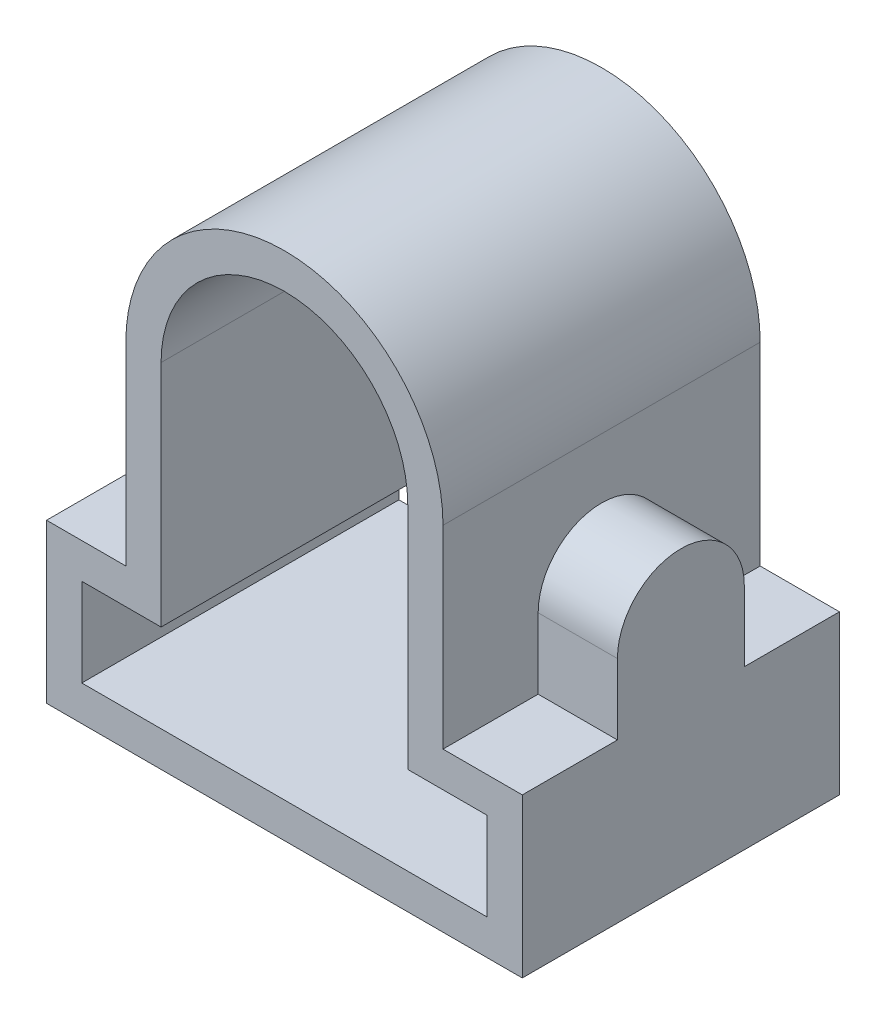
SolidWorks part; units mm, degrees
ref_plane "Front Plane" through (0, 0, 0) normal (0, 0, 1) x (1, 0, 0)
ref_plane "Top Plane" through (0, 0, 0) normal (0, 1, 0) x (1, 0, 0)
ref_plane "Right Plane" through (0, 0, 0) normal (1, 0, 0) x (0, 0, -1)
sketch "Sketch1" plane through (0, 0, 0) normal (0, 0, 1) x (1, 0, 0)
  line L0 (-67.5, 0) -> (67.5, 0)
  line L1 (67.5, 0) -> (67.5, 45)
  line L2 (67.5, 45) -> (45, 45)
  line L3 (45, 45) -> (45, 100)
  line L4 (0, 175.3726) -> (0, 0) construction
  line L5 (-67.5, 0) -> (-67.5, 45)
  line L6 (-67.5, 45) -> (-45, 45)
  line L7 (-45, 45) -> (-45, 100)
  line L8 (35, 35) -> (35, 100)
  line L9 (-35, 35) -> (-35, 100)
  line L10 (-57.5, 35) -> (-35, 35)
  line L11 (-57.5, 10) -> (-57.5, 35)
  line L12 (-57.5, 10) -> (57.5, 10)
  line L13 (57.5, 10) -> (57.5, 35)
  line L14 (57.5, 35) -> (35, 35)
  arc A0 (45, 100) -> (-45, 100) centre (0, 100) ccw
  arc A1 (35, 100) -> (-35, 100) centre (0, 100) ccw
  point P8 (0, 100)
  dimension "D4" = 90
  dimension "D1" = 45
  dimension "D2" = 67.5
  dimension "D3" = 100
  dimension "D5" = 10
extrude "Boss-Extrude1" add sketch "Sketch1" along normal blind 45 and the other way blind 45
sketch "Sketch2" plane through (67.5, 0, 0) normal (1, 0, 0) x (0, 0, -1)
  line L0 (0, 0) -> (0, 75.8758) construction
  line L1 (18, 65) -> (18, 45)
  line L2 (45, 45) -> (-45, 45) construction
  line L3 (-18, 65) -> (-18, 45)
  line L10 (-18, 45) -> (18, 45)
  arc A0 (18, 65) -> (-18, 65) centre (0, 65) ccw
  dimension "D2" = 36
  dimension "D1" = 65
extrude "Boss-Extrude2" add sketch "Sketch2" against normal blind 32
